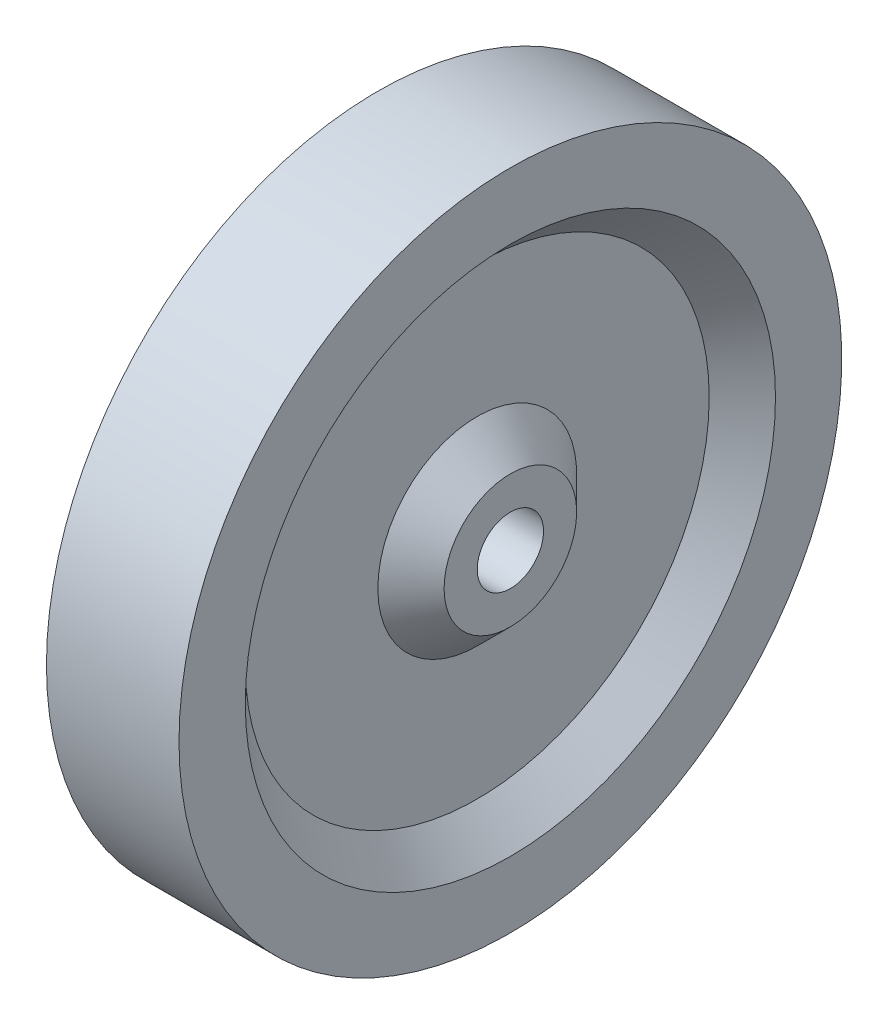
SolidWorks part; units mm, degrees
ref_plane "Front Plane" through (0, 0, 0) normal (0, 0, 1) x (1, 0, 0)
ref_plane "Top Plane" through (0, 0, 0) normal (0, 1, 0) x (1, 0, 0)
ref_plane "Right Plane" through (0, 0, 0) normal (1, 0, 0) x (0, 0, -1)
sketch "Sketch1" plane through (0, 0, 0) normal (0, 0, 1) x (1, 0, 0)
  line L0 (0, 7.907) -> (0, 25) construction
  line L1 (-10, 0) -> (-10, 10)
  line L2 (-10, 10) -> (-5, 15)
  line L3 (-5, 15) -> (-5, 35)
  line L4 (-5, 35) -> (-10, 40)
  line L5 (-10, 40) -> (-10, 50)
  line L6 (-10, 50) -> (10, 50)
  line L7 (10, 40) -> (10, 50)
  line L8 (5, 35) -> (10, 40)
  line L9 (5, 15) -> (5, 35)
  line L10 (10, 10) -> (5, 15)
  line L11 (10, 0) -> (10, 10)
  line L12 (-10, 0) -> (10, 0)
  line L13 (-10, 0) -> (10, 0)
  point P12 (0, 50)
  dimension "D1" = 10
  dimension "D2" = 50
  dimension "D3" = 10
  dimension "D4" = 10
  dimension "D5" = 45
  dimension "D6" = 45
  dimension "D7" = 5
revolve "Revolve1" add sketch "Sketch1" angle 360 about L12 region at (-9.4615, 5, 0)
ref_axis "Axis1" through (-10, 0, 0) along (1, 0, 0)
sketch "Sketch2" plane through (10, 0, 0) normal (1, 0, 0) x (0, 0, -1)
  circle A0 centre (0, 0) radius 5
extrude "Cut-Extrude1" cut sketch "Sketch2" against normal through all
